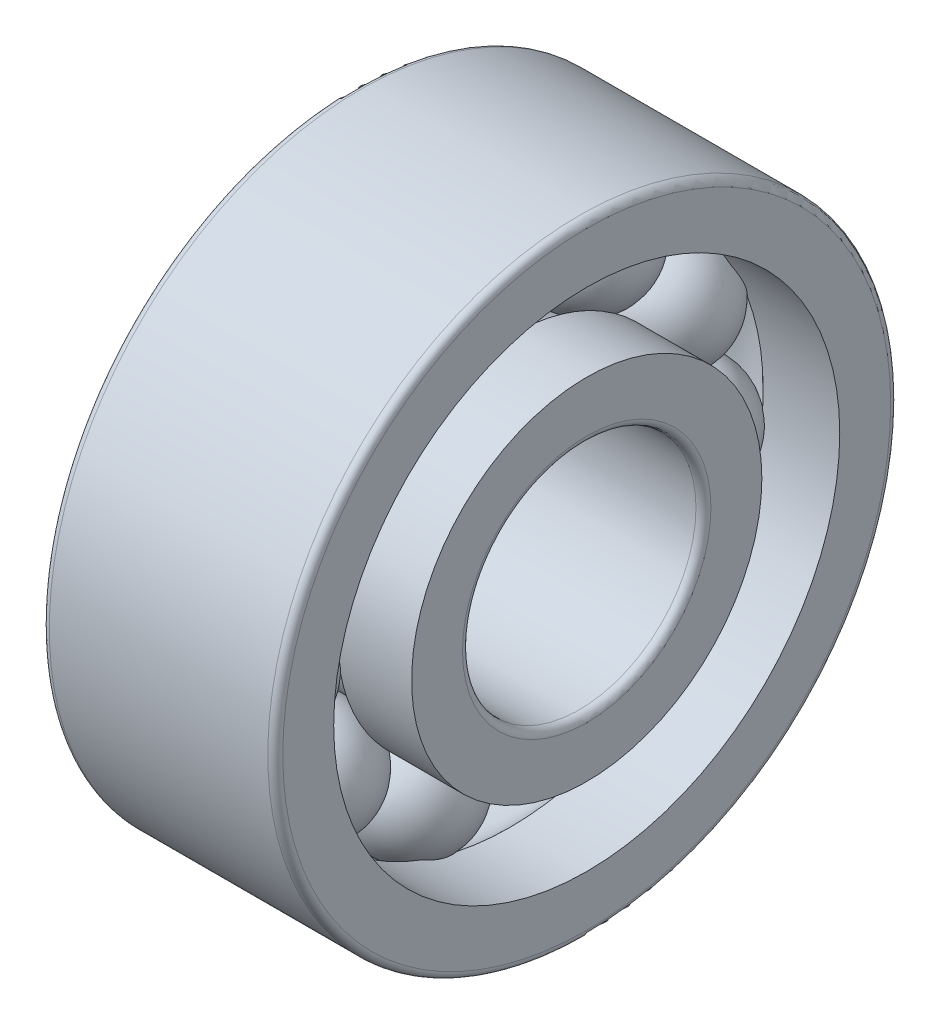
SolidWorks part; units mm, degrees
ref_plane "Plane1" through (0, 0, 0) normal (0, 0, 1) x (1, 0, 0)
ref_plane "Plane2" through (0, 0, 0) normal (0, 1, 0) x (1, 0, 0)
ref_plane "Plane3" through (0, 0, 0) normal (1, 0, 0) x (0, 0, -1)
other "Configuration Table"
sketch "Clipboard" plane through (0, 0, 0) normal (0, 0, 1) x (1, 0, 0)
  line L0 (-10, 0) -> (10, 0) construction
  line L1 (0, 0) -> (21.9499, -4.2666)
  line L2 (0, 0) -> (2.1822, -0.0381)
  line L3 (0, 0) -> (22.3573, 0.3902)
  line L4 (0, 0) -> (-22.3573, -0.3902)
  dimension "BallCLRad" = 2.1825
sketch "CagSpiSke" plane through (0, 0, 0) normal (0, 0, 1) x (1, 0, 0)
  line L0 (0.0596, 2.0832) -> (0.0596, 2.2817)
  line L1 (0.0596, 2.2817) -> (-0.0596, 2.2817)
  line L2 (-0.0596, 2.2817) -> (-0.0596, 2.0832)
  line L3 (-0.0596, 2.0832) -> (0.0596, 2.0832)
  line L4 (-20.6375, 0) -> (20.6375, 0) construction
  line L5 (0, 0) -> (0, 23.7692) construction
  dimension "OD" = 4.5635
  dimension "ID" = 4.1665
revolve "CageSpine" add sketch "CagSpiSke" angle 0.001 about L4 reverse direction yes
ref_axis "Axis1" through (-50, 0, 0) along (1, 0, 0)
sketch "CagBalSke" plane through (0, 0, 0) normal (0, 0, 1) x (1, 0, 0)
  line L0 (-0.6551, 2.1825) -> (0.6551, 2.1825)
  line L1 (-1.905, 2.1825) -> (1.905, 2.1825) construction
  line L2 (-10, 0) -> (10, 0) construction
  line L3 (0, 0) -> (0, 24) construction
  arc A0 (0.6551, 2.1825) -> (-0.6551, 2.1825) centre (0, 2.1825) cw
  dimension "BallCLRad" = 2.1825
revolve "CageBall" [suppressed] add sketch "CagBalSke" angle 360 about L1 reverse direction yes
pattern_circular "CageBalls" [suppressed] count 11 every 32.727 about axis through (-50, 0, 0) along (1, 0, 0)
sketch "CagTrmODSke" plane through (0, 0, 0) normal (0, 0, 1) x (1, 0, 0)
  line L0 (0.6805, 2.2817) -> (0.6805, 2.8629)
  line L1 (0.6805, 2.8629) -> (-0.6805, 2.8629)
  line L2 (-0.6805, 2.8629) -> (-0.6805, 2.2817)
  line L3 (-0.6805, 2.2817) -> (0.6805, 2.2817)
  line L4 (-20.6375, 0) -> (20.6375, 0) construction
  line L5 (0, 0) -> (0, 25) construction
  dimension "Width" = 1.3609
  dimension "ID" = 4.5635
  dimension "OD" = 5.7259
revolve "CageTrimOD" [suppressed] cut sketch "CagTrmODSke" angle 360 about L4 reverse direction yes
sketch "CagTrmIDSke" plane through (0, 0, 0) normal (0, 0, 1) x (1, 0, 0)
  line L0 (0.6805, 1.5528) -> (0.6805, 2.0832)
  line L1 (0.6805, 2.0832) -> (-0.6805, 2.0832)
  line L2 (-0.6805, 2.0832) -> (-0.6805, 1.5528)
  line L3 (-0.6805, 1.5528) -> (0.6805, 1.5528)
  line L4 (-20.6375, 0) -> (20.6375, 0) construction
  line L5 (0, 0) -> (0, 25) construction
  dimension "Width" = 1.3609
  dimension "ID" = 3.1057
  dimension "OD" = 4.1665
revolve "CageTrimID" [suppressed] cut sketch "CagTrmIDSke" angle 360 about L4 reverse direction yes
sketch "BalSimSke" plane through (0, 0, 0) normal (0, 0, 1) x (1, 0, 0)
  line L0 (-10, 0) -> (10, 0) construction
  line L1 (-10, 2.1825) -> (10, 2.1825) construction
  line L2 (0, 0) -> (0, 23) construction
  circle A0 centre (0, 2.1825) radius 0.5955
  dimension "BallCLRad" = 2.1825
  dimension "Ball_diameter" = 1.191
revolve "BallsSimplified" [suppressed] add sketch "BalSimSke" angle 360 about L0
sketch "BalDetSke" plane through (0, 0, 0) normal (0, 0, 1) x (1, 0, 0)
  line L0 (-0.5955, 2.1825) -> (0.5955, 2.1825)
  line L1 (-1.905, 2.1825) -> (1.905, 2.1825) construction
  line L2 (0, 0) -> (0, 25) construction
  arc A0 (0.5955, 2.1825) -> (-0.5955, 2.1825) centre (0, 2.1825) cw
  dimension "BallCLRad" = 2.1825
  dimension "Ball_diameter" = 1.191
revolve "BallDetailed" add sketch "BalDetSke" angle 360 about L1 reverse direction yes
sketch "InnRacSke" plane through (0, 0, 0) normal (0, 0, 1) x (1, 0, 0)
  line L0 (-0.3838, 1.7855) -> (-1.19, 1.7855)
  line L1 (-1.19, 1.7855) -> (-1.19, 1.2662)
  line L2 (-1.1138, 1.19) -> (1.1138, 1.19)
  line L3 (1.19, 1.2662) -> (1.19, 1.7855)
  line L4 (1.19, 1.7855) -> (0.4346, 1.7855)
  line L5 (-20.6375, 0) -> (20.6375, 0) construction
  line L6 (0, 0) -> (0, 30) construction
  arc A0 (-1.19, 1.2662) -> (-1.1138, 1.19) centre (-1.1138, 1.2662) ccw
  arc A1 (1.1138, 1.19) -> (1.19, 1.2662) centre (1.1138, 1.2662) ccw
  arc A2 (0.4346, 1.7855) -> (-0.3838, 1.7855) centre (0.0254, 2.1825) cw
  dimension "BallCLRad" = 2.1825
  dimension "Fillet_radius" = 0.0762
  dimension "Ball_diameter" = 1.1402
  dimension "ID" = 2.38
  dimension "OD" = 3.571
  dimension "Width" = 2.38
revolve "InnerRace" add sketch "InnRacSke" angle 360 about L5 reverse direction yes
sketch "OutRacSke" plane through (0, 0, 0) normal (0, 0, 1) x (1, 0, 0)
  line L0 (-0.4092, 2.5795) -> (-1.19, 2.5795)
  line L1 (-1.19, 2.5795) -> (-1.19, 3.0988)
  line L2 (-1.1138, 3.175) -> (1.1138, 3.175)
  line L3 (1.19, 3.0988) -> (1.19, 2.5795)
  line L4 (1.19, 2.5795) -> (0.4092, 2.5795)
  line L5 (-20.6375, 0) -> (20.6375, 0) construction
  line L6 (0, 0) -> (0, 30) construction
  arc A0 (-1.19, 3.0988) -> (-1.1138, 3.175) centre (-1.1138, 3.0988) cw
  arc A1 (1.1138, 3.175) -> (1.19, 3.0988) centre (1.1138, 3.0988) cw
  arc A2 (0.4092, 2.5795) -> (-0.4092, 2.5795) centre (0, 2.1825) ccw
  dimension "BallCLRad" = 2.1825
  dimension "Fillet_radius" = 0.0762
  dimension "Ball_diameter" = 1.1402
  dimension "Width" = 2.38
revolve "OuterRace" add sketch "OutRacSke" angle 360 about L5 reverse direction yes
pattern_circular "BallsDetailed" count 11 every 32.727 about axis through (-50, 0, 0) along (1, 0, 0) of "BallDetailed"
equation "\"BallCLRad@Clipboard\" = ( \"OD@OutRacSke\" + \"ID@InnRacSke\" ) / 4"
equation "\"BallCLRad@BalSimSke\" = \"BallCLRad@Clipboard\""
equation "\"BallCLRad@BalDetSke\" = \"BallCLRad@Clipboard\""
equation "\"BallCLRad@InnRacSke\" = \"BallCLRad@Clipboard\""
equation "\"BallCLRad@OutRacSke\" = \"BallCLRad@Clipboard\""
equation "\"Ball_diameter@InnRacSke\" = \"Ball_diameter@BalDetSke\" - 0.002"
equation "\"Ball_diameter@OutRacSke\" = \"Ball_diameter@BalDetSke\" - 0.002"
equation "\"Ball_diameter@BalSimSke\" = \"Ball_diameter@BalDetSke\""
equation "\"Width@OutRacSke\" = \"Width@InnRacSke\""
equation "\"Fillet_radius@OutRacSke\" = \"Fillet_radius@InnRacSke\""
equation "\"Max_count@Clipboard\" = int( 3.14159265 / atn(( \"Ball_diameter@BalDetSke\" / 2) / sqr( \"BallCLRad@Clipboard\"  *  \"BallCLRad@Clipboard\" - ( \"Ball_diameter@BalDetSke\" / 2) *  ( \"Ball_diameter@BalDetSke\" / 2))))"
equation "\"Max_count@Clipboard\" = ((sgn( \"Max_count@Clipboard\" - \"Count@Clipboard\" )-1)*( \"Max_count@Clipboard\" - \"Count@Clipboard\" ))/-2+ \"Count@Clipboard\""
equation "\"Count@BallsDetailed\" = int( \"Show_count@Clipboard\" ) "
equation "\"Count@BallsDetailed\" = ((sgn( \"Count@BallsDetailed\" - \"Max_count@Clipboard\" )-1)*( \"Count@BallsDetailed\" - \"Max_count@Clipboard\" ))/-2+ \"Max_count@Clipboard\""
equation "\"Count@BallsDetailed\" = ((sgn( \"Count@BallsDetailed\" - \"Min_count@Clipboard\" )+1)*( \"Count@BallsDetailed\" - \"Min_count@Clipboard\"))/2 +\"Min_count@Clipboard\""
equation "\"Angle@BallsDetailed\" = 360.0 / \"Max_count@Clipboard\""
equation "\"BallCLRad@CagBalSke\" = \"BallCLRad@Clipboard\""
equation "\"Count@CageBalls\" = \"Count@BallsDetailed\""
equation "\"Angle@CageBalls\" = \"Angle@BallsDetailed\""
equation "\"Angle@CageSpine\" =  \"Angle@CageBalls\" * ( \"Count@CageBalls\" -1 + int( \"Count@CageBalls\" / \"Max_count@Clipboard\" ) )  + 0.001 -  int( \"Count@CageBalls\" / \"Max_count@Clipboard\" ) * 0.001"
equation "\"Angle@CageSpine\" =  \"Angle@CageSpine\" * int( \"Min_count@Clipboard\" / 2) + int(1 / \"Min_count@Clipboard\")  * 0.001"
equation "\"CageWallOD@CagBalSke\" =  \"Ball_diameter@BalDetSke\" * 1.1"
equation "\"Thickness@CagSpiSke\" =  \"Ball_diameter@BalDetSke\" * 0.1"
equation "\"OD@CagTrmODSke\" = \"BallCLRad@Clipboard\" * 2 + \"CageWallOD@CagBalSke\" + 0.002"
equation "\"ID@CagTrmODSke\" = \"BallCLRad@Clipboard\" * 2 + \"Ball_diameter@BalDetSke\" / 6"
equation "\"OD@CagTrmIDSke\" = \"BallCLRad@Clipboard\" * 2 - \"Ball_diameter@BalDetSke\" / 6"
equation "\"ID@CagTrmIDSke\" = \"BallCLRad@Clipboard\" * 2 - \"CageWallOD@CagBalSke\" + 0.002"
equation "\"OD@CagSpiSke\" = \"ID@CagTrmODSke\""
equation "\"ID@CagSpiSke\" = \"OD@CagTrmIDSke\""
equation "\"Width@CagTrmODSke\" = \"CageWallOD@CagBalSke\" + 0.002"
equation "\"Width@CagTrmIDSke\" = \"CageWallOD@CagBalSke\" + 0.002"
